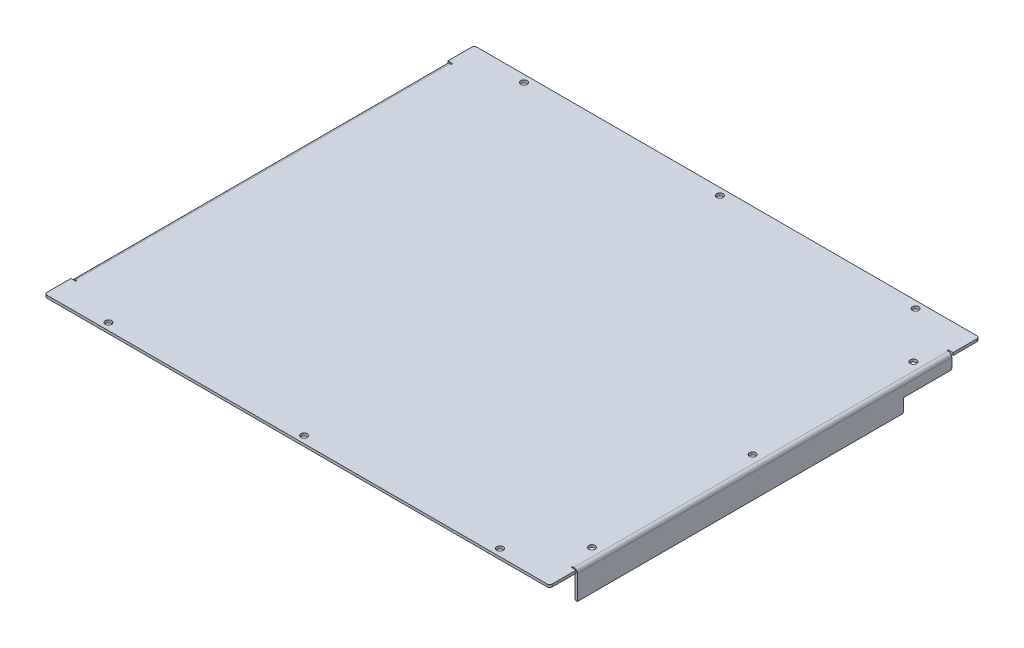
SolidWorks part; units mm, degrees
note: The reader was unsure of these and kept them because the rebuilt part matched: flange length of "Edge-Flange1".
material "ASTM A36 Steel"
ref_plane "Front Plane" through (0, 0, 0) normal (0, 0, 1) x (1, 0, 0)
ref_plane "Top Plane" through (0, 0, 0) normal (0, 1, 0) x (1, 0, 0)
ref_plane "Right Plane" through (0, 0, 0) normal (1, 0, 0) x (0, 0, -1)
sketch "Sketch1" plane through (0, 0, 0) normal (0, 1, 0) x (1, 0, 0)
  line L1 (-195.7, 166.5) -> (195.7, 166.5)
  line L2 (-195.7, 166.5) -> (-195.7, -166.5)
  line L3 (-195.7, -166.5) -> (195.7, -166.5)
  line L4 (195.7, 166.5) -> (195.7, -166.5)
  line L5 (-195.7, 166.5) -> (195.7, -166.5) construction
  line L6 (-195.7, -166.5) -> (195.7, 166.5) construction
  point P0 (0, 0)
  dimension "D1" = 333
  dimension "D2" = 391.4
base flange "Base-Flange1" sketch "Sketch1" thickness 2 reverse thickness direction yes parameters "D1"=0.7366
edge flange "Edge-Flange1" sketch "Sketch6" flange profiles "Sketch6", "Sketch7" flange angle 90 flange length 21.5 flange position material inside bend radius 0.7366 thickness 2 relief rectangular parameters "D6"=10, "D8"=1
sketch "Sketch6" plane through (-195.7, 0, 0) normal (-1, 0, 0) x (0, 0, -1)
  line L0 (166.5, 0) -> (-166.5, 0) construction
  line L1 (145, 0) -> (-145, 0)
  line L2 (-145, 0) -> (-145, 19.5)
  line L3 (-145, 19.5) -> (145, 19.5)
  line L4 (145, 19.5) -> (145, 0)
  line L5 (0, 86.0405) -> (0, -54.931) construction
  dimension "D1" = 290
sketch "Sketch7" plane through (195.7, 0, 0) normal (1, 0, 0) x (0, 0, 1)
  line L0 (166.5, 0) -> (-166.5, 0) construction
  line L1 (145, 0) -> (-145, 0)
  line L2 (-145, 0) -> (-145, 19.5)
  line L3 (-145, 19.5) -> (145, 19.5)
  line L4 (145, 19.5) -> (145, 0)
  line L5 (0, 32.6877) -> (0, -21.7478) construction
  dimension "D1" = 290
bend "EdgeBend1" bend radius 0.7366 bend angle 90 parameters "D5"=1
bend "EdgeBend2" bend radius 0.7366 bend angle 90 parameters "D5"=2
fillet "Fillet1" radius 2 4 edges at (-195.7, 1, 166.5) (195.7, 1, 166.5) (195.7, 1, -166.5) (-195.7, 1, -166.5)
sketch "Sketch8" plane through (195.7, 0, 0) normal (1, 0, 0) x (0, 0, -1)
  line L0 (-145, -19.5) -> (145, -19.5) construction
  line L1 (107.5, -19.5) -> (147.8555, -19.5)
  line L2 (107.5, -19.5) -> (107.5, -10)
  line L3 (108.5, -9) -> (147.8555, -9)
  line L4 (147.8555, -19.5) -> (147.8555, -9)
  line L5 (139.5, -10) -> (111.5, -10) construction
  line L6 (108.5, -13) -> (108.5, -41) construction
  arc A0 (107.5, -10) -> (108.5, -9) centre (108.5, -10) cw
  dimension "D3" = 1
  dimension "D1" = 1
  dimension "D2" = 1
extrude "Cut-Extrude1" cut sketch "Sketch8" against normal blind 10 normal cut yes
fillet "Fillet2" radius 1 2 edges at (194.7, -19.5, -107.5) (194.7, -9, -145)
sketch "Sketch9" plane through (0, 2, 0) normal (0, 1, 0) x (1, 0, 0)
  line L0 (-193.7, -166.5) -> (193.7, -166.5) construction
  line L1 (192.9634, -145) -> (192.9634, 145) construction
  line L2 (193.7, 166.5) -> (-193.7, 166.5) construction
  line L3 (-181.7, -166.5) -> (-181.7, 166.5) construction
  line L4 (-195.7, 164.5) -> (-195.7, 146) construction
  line L5 (181.7, -166.5) -> (181.7, 166.5) construction
  line L6 (195.7, 146) -> (195.7, 164.5) construction
  line L7 (195.7, 154.5) -> (-195.7, 154.5) construction
  line L8 (-195.7, -154.5) -> (195.7, -154.5) construction
  line L9 (-195.7, -146) -> (-195.7, -164.5) construction
  line L10 (195.7, -164.5) -> (195.7, -146) construction
  line L11 (0, 154.5) -> (0, -154.5) construction
  line L12 (-181.7, 0) -> (181.7, 0) construction
  circle A0 centre (-151.7, -161) radius 2.5
  circle A1 centre (0, -161) radius 2.5
  circle A2 centre (151.7, -161) radius 2.5
  circle A3 centre (186.4634, -124.5) radius 2.5
  circle A4 centre (186.4634, 0) radius 2.5
  circle A5 centre (186.4634, 124.5) radius 2.5
  circle A6 centre (151.7, 161) radius 2.5
  circle A7 centre (0, 161) radius 2.5
  circle A8 centre (-151.7, 161) radius 2.5
  dimension "D1" = 5
  dimension "D2" = 5.5
  dimension "D3" = 6.5
  dimension "D4" = 5.5
  dimension "D5" = 14
  dimension "D6" = 14
  dimension "D7" = 12
  dimension "D8" = 12
  dimension "D9" = 181.7
  dimension "D10" = 154.5
  dimension "D11" = 30
  dimension "D12" = 30
  dimension "D13" = 30
  dimension "D14" = 30
extrude "Cut-Extrude2" cut sketch "Sketch9" against normal through all both normal cut yes
sketch "Bend-Lines1" [suppressed] plane through (0, 0, 0) normal (0, 1, 0) x (1, 0, 0)
sketch "Bounding-Box1" [suppressed] plane through (0, 0, 0) normal (0, 1, 0) x (1, 0, 0)
sheet metal parameters "Sheet-Metal1" thickness 2 parameters "D1"=0.7366
flat pattern "Flat-Pattern1" [suppressed]
sketch "Bend-Lines2" plane through (0, 0, 0) normal (0, 1, 0) x (1, 0, 0)
sketch3d "Bounding-Box2" [suppressed]
  line L0 (195.7, -166.5, 0) -> (-195.7, -166.5, 0) construction
  line L1 (195.7, 166.5, 0) -> (-195.7, 166.5, 0) construction
  line L2 (195.7, -166.5, 0) -> (195.7, 166.5, 0) construction
  line L3 (-195.7, -166.5, 0) -> (-195.7, 166.5, 0) construction
sheet metal parameters "Sheet-Metal2" thickness 2 parameters "D1"=0.7366
flat pattern "Flat-Pattern1"
sketch "Bend-Lines2" plane through (0, 0, 0) normal (0, -1, 0) x (-1, 0, 0)
  line L0 (-194.3273, 145) -> (-194.3273, -145) construction
  line L1 (194.3273, -145) -> (194.3273, 145) construction
  line L2 (-194.3273, 145) -> (-194.3273, -145) construction
  line L3 (194.3273, -145) -> (194.3273, 145) construction
sketch3d "Bounding-Box2" [suppressed]
  line L0 (-214.4546, -166.5, 0) -> (214.4546, -166.5, 0) construction
  line L1 (-214.4546, 166.5, 0) -> (214.4546, 166.5, 0) construction
  line L2 (-214.4546, -166.5, 0) -> (-214.4546, 166.5, 0) construction
  line L3 (214.4546, -166.5, 0) -> (214.4546, 166.5, 0) construction
bend of the flat pattern "Flatten-<EdgeBend1>1"
bend of the flat pattern "Flatten-<EdgeBend2>1"
sheet metal parameters "Sheet-Metal3" thickness 2 parameters "D1"=0.7366
flat pattern "Flat-Pattern1"
sketch "Bend-Lines2" plane through (0, 0, 0) normal (0, -1, 0) x (-1, 0, 0)
  line L0 (-194.3273, 145) -> (-194.3273, -145) construction
  line L1 (194.3273, -145) -> (194.3273, 145) construction
  line L2 (-194.3273, 145) -> (-194.3273, -145) construction
  line L3 (194.3273, -145) -> (194.3273, 145) construction
sketch3d "Bounding-Box2" [suppressed]
  line L0 (-214.4546, -166.5, 0) -> (214.4546, -166.5, 0) construction
  line L1 (-214.4546, 166.5, 0) -> (214.4546, 166.5, 0) construction
  line L2 (-214.4546, -166.5, 0) -> (-214.4546, 166.5, 0) construction
  line L3 (214.4546, -166.5, 0) -> (214.4546, 166.5, 0) construction
bend of the flat pattern "Flatten-<EdgeBend1>1"
bend of the flat pattern "Flatten-<EdgeBend2>1"
sheet metal parameters "Sheet-Metal4" thickness 2 parameters "D1"=0.7366
flat pattern "Flat-Pattern1"
sketch "Bend-Lines2" plane through (0, 0, 0) normal (0, -1, 0) x (-1, 0, 0)
  line L0 (-194.3273, 145) -> (-194.3273, -145) construction
  line L1 (194.3273, -145) -> (194.3273, 145) construction
  line L2 (-194.3273, 145) -> (-194.3273, -145) construction
  line L3 (194.3273, -145) -> (194.3273, 145) construction
sketch3d "Bounding-Box2" [suppressed]
  line L0 (-214.4546, -166.5, 0) -> (214.4546, -166.5, 0) construction
  line L1 (-214.4546, 166.5, 0) -> (214.4546, 166.5, 0) construction
  line L2 (-214.4546, -166.5, 0) -> (-214.4546, 166.5, 0) construction
  line L3 (214.4546, -166.5, 0) -> (214.4546, 166.5, 0) construction
bend of the flat pattern "Flatten-<EdgeBend1>1"
bend of the flat pattern "Flatten-<EdgeBend2>1"
